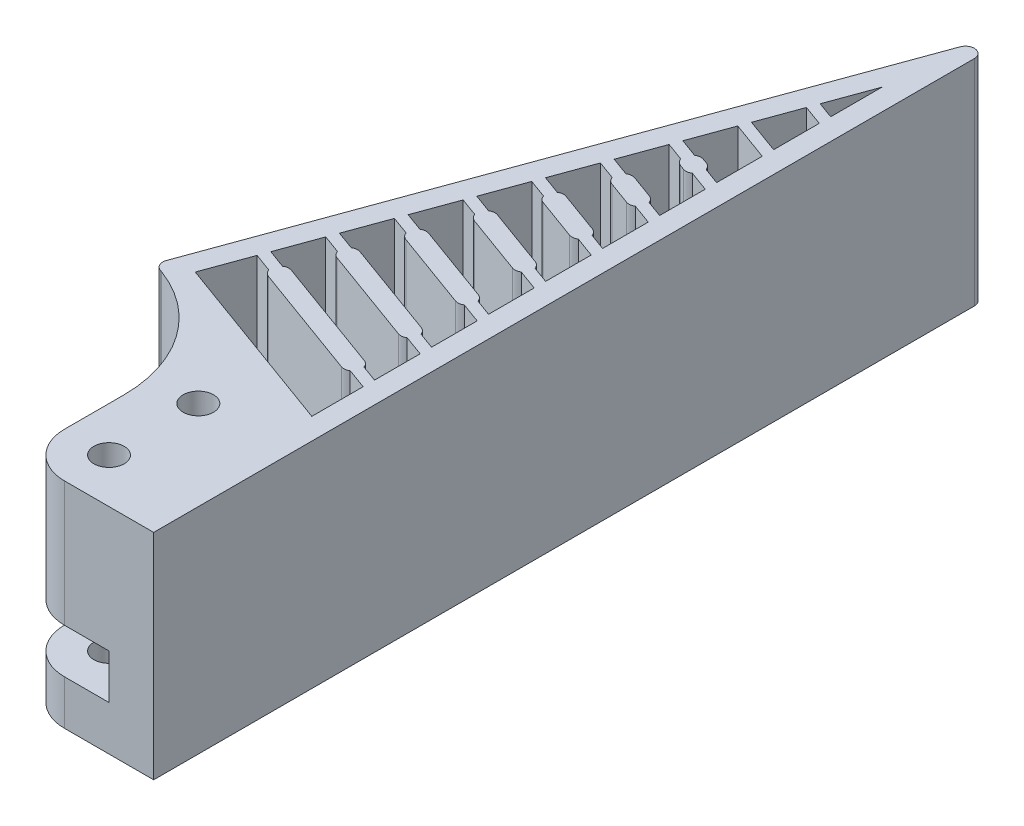
SolidWorks part; units mm, degrees
ref_plane "前视基准面" through (0, 0, 0) normal (0, 0, 1) x (1, 0, 0)
ref_plane "上视基准面" through (0, 0, 0) normal (0, 1, 0) x (1, 0, 0)
ref_plane "右视基准面" through (0, 0, 0) normal (1, 0, 0) x (0, 0, -1)
sketch "草图1" plane through (0, 0, 0) normal (0, 1, 0) x (1, 0, 0)
  line L0 (0, 0) -> (0, 10) construction
  line L1 (-5, 0) -> (-5, 17.1407)
  line L2 (0, -5) -> (10, -5)
  line L4 (-15.9973, 21.1434) -> (10, 92.5705)
  line L12 (10, 92.5705) -> (10, 11.6812)
  line L13 (10, 11.6812) -> (10, -5)
  line L15 (-12.9212, 22.5779) -> (7.6, 78.9594)
  line L16 (7.6, 78.9594) -> (7.6, 15.1087)
  line L17 (7.6, 15.1087) -> (-12.9212, 22.5779)
  line L18 (-10.8691, 28.216) -> (-8.05, 27.1899) construction
  line L19 (-8.05, 27.1899) -> (4.7809, 22.5199) construction
  line L20 (4.7809, 22.5199) -> (7.6, 21.4938) construction
  line L21 (-8.05, 27.1899) -> (4.7809, 22.5199) construction
  line L24 (-7.708, 28.1296) -> (5.1229, 23.4596)
  line L25 (-8.392, 26.2503) -> (4.4389, 21.5802)
  line L26 (-10.6639, 28.7798) -> (-8.5966, 28.0274)
  line L27 (-11.0743, 27.6522) -> (-9.007, 26.8997)
  line L28 (5.7379, 22.8101) -> (7.6, 22.1323)
  line L29 (5.3275, 21.6824) -> (7.6, 20.8553)
  line L30 (-8.817, 33.8542) -> (-5.9979, 32.8281) construction
  line L31 (-5.9979, 32.8281) -> (4.7809, 28.9049) construction
  line L32 (4.7809, 28.9049) -> (7.6, 27.8789) construction
  line L33 (-5.9979, 32.8281) -> (4.7809, 28.9049) construction
  line L34 (-5.6559, 33.7678) -> (5.1229, 29.8446)
  line L35 (-6.3399, 31.8884) -> (4.4389, 27.9652)
  line L36 (-8.6118, 34.418) -> (-6.5444, 33.6655)
  line L37 (-9.0222, 33.2903) -> (-6.9549, 32.5379)
  line L38 (5.7379, 29.1951) -> (7.6, 28.5174)
  line L39 (5.3275, 28.0675) -> (7.6, 27.2404)
  line L40 (-6.7648, 39.4923) -> (-3.9458, 38.4663) construction
  line L41 (-3.9458, 38.4663) -> (4.7809, 35.29) construction
  line L42 (4.7809, 35.29) -> (7.6, 34.2639) construction
  line L43 (-3.9458, 38.4663) -> (4.7809, 35.29) construction
  line L44 (-3.6037, 39.406) -> (5.1229, 36.2297)
  line L45 (-4.2878, 37.5266) -> (4.4389, 34.3503)
  line L46 (-6.5596, 40.0561) -> (-4.4923, 39.3037)
  line L47 (-6.9701, 38.9285) -> (-4.9027, 38.1761)
  line L48 (5.7379, 35.5802) -> (7.6, 34.9024)
  line L49 (5.3275, 34.4526) -> (7.6, 33.6254)
  line L50 (-4.7127, 45.1305) -> (-1.8936, 44.1044) construction
  line L51 (-1.8936, 44.1044) -> (4.7809, 41.6751) construction
  line L52 (4.7809, 41.6751) -> (7.6, 40.649) construction
  line L53 (-1.8936, 44.1044) -> (4.7809, 41.6751) construction
  line L56 (-1.5516, 45.0441) -> (5.1229, 42.6148)
  line L57 (-2.2357, 43.1647) -> (4.4389, 40.7354)
  line L58 (-4.5075, 45.6943) -> (-2.4402, 44.9418)
  line L59 (-4.9179, 44.5667) -> (-2.8506, 43.8142)
  line L60 (-5, 17.1407) -> (10, 11.6812) construction
  line L70 (5.7379, 41.9653) -> (7.6, 41.2875)
  line L71 (5.3275, 40.8376) -> (7.6, 40.0105)
  line L72 (-12.9212, 22.5779) -> (7.6, 15.1087) construction
  line L73 (-15.9973, 21.1434) -> (10, 11.6812) construction
  line L74 (-15.9973, 21.1434) -> (-5, 17.1407)
  line L76 (10, 11.6812) -> (-5, 11.6812) construction
  line L77 (-2.6606, 50.7686) -> (0.1585, 49.7426) construction
  line L78 (0.1585, 49.7426) -> (4.7809, 48.0601) construction
  line L79 (4.7809, 48.0601) -> (7.6, 47.0341) construction
  line L80 (0.1585, 49.7426) -> (4.7809, 48.0601) construction
  line L81 (0.5005, 50.6823) -> (5.1229, 48.9998)
  line L82 (-0.1835, 48.8029) -> (4.4389, 47.1204)
  line L83 (-2.4554, 51.3324) -> (-0.3881, 50.58)
  line L84 (-2.8658, 50.2048) -> (-0.7985, 49.4524)
  line L85 (5.7379, 48.3503) -> (7.6, 47.6726)
  line L86 (5.3275, 47.2227) -> (7.6, 46.3956)
  line L87 (-0.6085, 56.4068) -> (2.2106, 55.3807) construction
  line L88 (2.2106, 55.3807) -> (4.7809, 54.4452) construction
  line L89 (4.7809, 54.4452) -> (7.6, 53.4191) construction
  line L90 (2.2106, 55.3807) -> (4.7809, 54.4452) construction
  line L91 (2.5526, 56.3204) -> (5.1229, 55.3849)
  line L92 (1.8686, 54.441) -> (4.4389, 53.5055)
  line L93 (-0.4033, 56.9706) -> (1.6641, 56.2182)
  line L94 (-0.8137, 55.843) -> (1.2536, 55.0905)
  line L95 (5.7379, 54.7354) -> (7.6, 54.0576)
  line L96 (5.3275, 53.6078) -> (7.6, 52.7806)
  line L97 (1.4436, 62.0449) -> (4.2627, 61.0189) construction
  line L98 (4.2627, 61.0189) -> (4.7809, 60.8303) construction
  line L99 (4.7809, 60.8303) -> (7.6, 59.8042) construction
  line L100 (4.2627, 61.0189) -> (4.7809, 60.8303) construction
  line L101 (4.6047, 61.9586) -> (5.1229, 61.77)
  line L102 (3.9207, 60.0792) -> (4.4389, 59.8906)
  line L103 (1.6488, 62.6088) -> (3.7162, 61.8563)
  line L104 (1.2384, 61.4811) -> (3.3057, 60.7287)
  line L105 (5.7379, 61.1205) -> (7.6, 60.4427)
  line L106 (5.3275, 59.9928) -> (7.6, 59.1657)
  line L107 (3.4958, 67.6831) -> (7.6, 66.1893) construction
  line L108 (5.5479, 73.3213) -> (7.6, 72.5743) construction
  line L111 (5.3427, 72.7574) -> (7.6, 71.9358)
  line L112 (3.2905, 67.1193) -> (7.6, 65.5508)
  line L114 (5.7531, 73.8851) -> (7.6, 73.2128)
  line L115 (3.701, 68.2469) -> (7.6, 66.8278)
  line L116 (3.701, 68.2469) -> (7.8052, 66.7531) construction
  line L117 (3.2905, 67.1193) -> (7.3948, 65.6255) construction
  line L118 (5.7531, 73.8851) -> (7.8052, 73.1382) construction
  line L119 (5.3427, 72.7574) -> (7.3948, 72.0105) construction
  circle A0 centre (0, 0) radius 1.7
  circle A1 centre (0, 10) radius 1.7
  arc A2 (-5, 0) -> (0, -5) centre (0, 0) ccw
  arc A5 (-7.708, 28.1296) -> (-8.392, 26.2503) centre (-8.05, 27.1899) ccw
  arc A6 (4.4389, 21.5802) -> (5.1229, 23.4596) centre (4.7809, 22.5199) ccw
  arc A7 (-5.6559, 33.7678) -> (-6.3399, 31.8884) centre (-5.9979, 32.8281) ccw
  arc A8 (4.4389, 27.9652) -> (5.1229, 29.8446) centre (4.7809, 28.9049) ccw
  arc A9 (-3.6037, 39.406) -> (-4.2878, 37.5266) centre (-3.9458, 38.4663) ccw
  arc A10 (4.4389, 34.3503) -> (5.1229, 36.2297) centre (4.7809, 35.29) ccw
  arc A17 (-1.5516, 45.0441) -> (-2.2357, 43.1647) centre (-1.8936, 44.1044) ccw
  arc A18 (4.4389, 40.7354) -> (5.1229, 42.6148) centre (4.7809, 41.6751) ccw
  arc A19 (0.5005, 50.6823) -> (-0.1835, 48.8029) centre (0.1585, 49.7426) ccw
  arc A20 (4.4389, 47.1204) -> (5.1229, 48.9998) centre (4.7809, 48.0601) ccw
  arc A21 (2.5526, 56.3204) -> (1.8686, 54.441) centre (2.2106, 55.3807) ccw
  arc A22 (4.4389, 53.5055) -> (5.1229, 55.3849) centre (4.7809, 54.4452) ccw
  arc A23 (4.6047, 61.9586) -> (3.9207, 60.0792) centre (4.2627, 61.0189) ccw
  arc A24 (4.4389, 59.8906) -> (5.1229, 61.77) centre (4.7809, 60.8303) ccw
  circle A25 centre (0, 10) radius 5 construction
  point P17 (-1.6345, 24.8549)
  point P35 (-0.6085, 30.8665)
  point P50 (2.4697, 48.9014)
  point P62 (0.4176, 36.8781)
  point P88 (1.4436, 42.8897)
  point P122 (6.5739, 72.9478)
  point P124 (-1.4217, 50.9562)
  point P131 (3.4958, 54.913)
  point P156 (4.5218, 60.9246)
  dimension "D1" = 3.4
  dimension "D3" = 5
  dimension "D6" = 2.4
  dimension "D5" = 10
  dimension "D2" = 10
  dimension "D7" = 20
  dimension "D8" = 2
  dimension "D9" = 0.6
  dimension "D10" = 0.6
  dimension "D11" = 0.6
  dimension "D12" = 0.6
  dimension "D13" = 3
  dimension "D14" = 3
  dimension "D15" = 6
  dimension "D16" = 0.6
  dimension "D17" = 0.6
  dimension "D18" = 0.6
  dimension "D19" = 0.6
  dimension "D20" = 3
  dimension "D21" = 2
  dimension "D22" = 6
  dimension "D23" = 60
  dimension "D24" = 0.6
  dimension "D25" = 0.6
  dimension "D26" = 0.6
  dimension "D27" = 0.6
  dimension "D28" = 2
  dimension "D29" = 6
  dimension "D30" = 6
  dimension "D31" = 0.6
  dimension "D32" = 3
  dimension "D33" = 0.6
  dimension "D34" = 2
  dimension "D35" = 0.6
  dimension "D36" = 0.6
  dimension "D37" = 0.6
  dimension "D38" = 0.6
  dimension "D39" = 6
  dimension "D40" = 2
  dimension "D41" = 3
  dimension "D42" = 0.6
  dimension "D43" = 6
  dimension "D44" = 3
  dimension "D45" = 2
  dimension "D46" = 0.6
  dimension "D47" = 2
  dimension "D48" = 6
  dimension "D49" = 3
  dimension "D50" = 6
  dimension "D51" = 6
  dimension "D53" = 0.6
  dimension "D54" = 0.6
extrude "凸台-拉伸1" add sketch "草图1" along normal blind 24 contours L1 A2 L2 L13 L12 L4 L74 L16 L17 L15 | L114 L15 L111 L16 | L115 L15 L112 L16 | A23 L103 L15 L104 | A24 L101 A23 L102 | A24 L106 L16 L105 | A22 L96 L16 L95 | A22 L91 A21 L92 | A21 L93 L15 L94 | A19 L83 L15 L84 | A20 L81 A19 L82 | A20 L86 L16 L85 | A18 L71 L16 L70 | A18 L56 A17 L57 | A17 L58 L15 L59 | A9 L46 L15 L47 | A10 L44 A9 L45 | A10 L49 L16 L48 | A8 L39 L16 L38 | A8 L34 A7 L35 | A7 L36 L15 L37 | A5 L26 L15 L27 | A6 L24 A5 L25 | A6 L29 L16 L28 region at (-3.9903, 0, -8.5704) region at (-9.8987, 0, -27.8628) region at (-1.6345, 0, -24.8549) region at (6.626, 0, -21.8258) region at (-7.8465, 0, -33.501) region at (-0.6085, 0, -30.8665) region at (6.626, 0, -28.2109) region at (-5.7944, 0, -39.1391) region at (0.4176, 0, -36.8781) region at (6.626, 0, -34.5959) region at (-3.7423, 0, -44.7773) region at (1.4436, 0, -42.8897) region at (6.626, 0, -40.981) region at (-1.6902, 0, -50.4154) region at (2.4697, 0, -48.9014) region at (6.626, 0, -47.3661) region at (0.3619, 0, -56.0536) region at (3.4958, 0, -54.913) region at (6.626, 0, -53.7511) region at (2.4141, 0, -61.6917) region at (4.5218, 0, -60.9246) region at (6.626, 0, -60.1362) region at (5.5462, 0, -66.9262) region at (6.5705, 0, -72.9278)
sketch "草图2" plane through (0, 0, 0) normal (0, -1, 0) x (1, 0, 0)
  line L0 (-5, 0) -> (-5, -17.1407) construction
  line L1 (-5, -15) -> (5, -15)
  line L2 (-5, -15) -> (-5, 5)
  line L3 (-5, 5) -> (5, 5)
  line L4 (5, -15) -> (5, 5)
  line L5 (0, 5) -> (10, 5) construction
  circle A0 centre (0, 0) radius 1.7 construction
  circle A1 centre (0, 0) radius 1.7
  circle A2 centre (0, -10) radius 1.7 construction
  circle A3 centre (0, -10) radius 1.7
  arc A4 (5, -10.2) -> (0.2, -15) centre (0.2, -10.2) cw
  point P14 (5, -5)
  dimension "D2" = 5
  dimension "D3" = 4.8
  dimension "D1" = 10
extrude "切除-拉伸1" cut sketch "草图2" against normal blind 5 from offset 5 contours A4 L4 L3 L2 L1 A3 A1 region at (-0.1098, 0, -4.7505) offset against normal yes
fillet "圆角1" radius 1 2 edges at (-15.9973, 12, -21.1434) (10, 12, -92.5705)
fillet "圆角2" radius 15 1 edges at (-5, 12, -17.1407)
